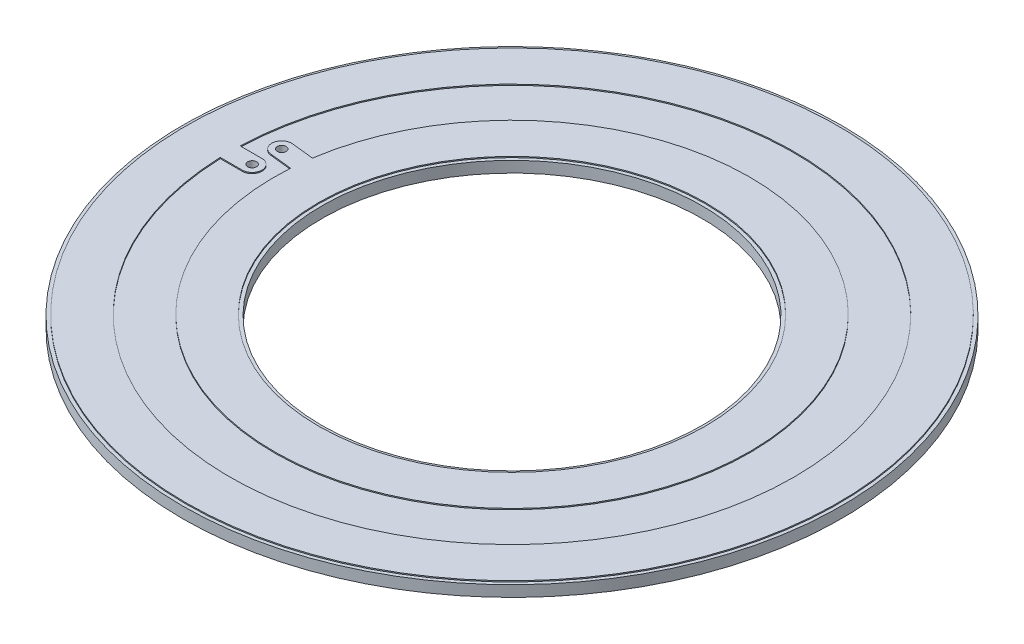
SolidWorks part; units mm, degrees
ref_plane "Спереди" through (0, 0, 0) normal (0, 0, 1) x (1, 0, 0)
ref_plane "Сверху" through (0, 0, 0) normal (0, 1, 0) x (1, 0, 0)
ref_plane "Справа" through (0, 0, 0) normal (1, 0, 0) x (0, 0, -1)
sketch "Эскиз1" plane through (0, 0, 0) normal (0, 1, 0) x (1, 0, 0)
  circle A0 centre (0, 0) radius 17.2
  circle A1 centre (0, 0) radius 29.8
  dimension "D1" = 34.4
  dimension "D2" = 59.6
extrude "Бобышка-Вытянуть1" add sketch "Эскиз1" along normal blind 1
sketch "Эскиз2" plane through (0, 1, 0) normal (0, 1, 0) x (1, 0, 0)
  circle A0 centre (0, 0) radius 29.5
  circle A1 centre (0, 0) radius 25.5
  circle A2 centre (0, 0) radius 21.5
  circle A3 centre (0, 0) radius 17.5
  circle A5 centre (0, 0) radius 17.2 construction
  dimension "D1" = 4
  dimension "D2" = 4
  dimension "D3" = 4
  dimension "D4" = 0.3
extrude "Бобышка-Вытянуть2" add sketch "Эскиз2" along normal blind 0.1 contours A2 A3 | A0 A1 region at (-28.6656, 1, 0) region at (-20.8919, 1, 0)
sketch "Эскиз4" plane through (0, 1, 0) normal (0, 1, 0) x (1, 0, 0)
  line L0 (0, 0) -> (-33.7363, 0) construction
  circle A0 centre (-23.5, 0) radius 0.4
  circle A1 centre (-23.3623, 2.54) radius 0.4
  circle A3 centre (0, 0) radius 23.5 construction
  circle A4 centre (0, 0) radius 21.5 construction
  dimension "D1" = 2
  dimension "D2" = 0.8
  dimension "D3" = 0.8
  dimension "D5" = 47
  dimension "D4" = 2.54
extrude "Вырез-Вытянуть1" cut sketch "Эскиз4" against normal through all
sketch "Эскиз5" plane through (0, 1, 0) normal (0, 1, 0) x (1, 0, 0)
  circle A0 centre (-23.3623, 2.54) radius 0.9
  circle A1 centre (-23.5, 0) radius 0.4 construction
  circle A3 centre (-23.5, 0) radius 0.9
  circle A4 centre (-23.5, 0) radius 0.4
  circle A5 centre (-23.3623, 2.54) radius 0.4 construction
  circle A6 centre (-23.3623, 2.54) radius 0.4
  dimension "D2" = 1.8
  dimension "D1" = 1.8
extrude "Бобышка-Вытянуть3" add sketch "Эскиз5" along normal blind 0.1
ref_axis "Ось1" through (0, 1, 0) along (0, -1, 0)
sketch "Эскиз6" plane through (0, 1, 0) normal (0, 1, 0) x (1, 0, 0)
  line L2 (-23.3623, 2.54) -> (0, 0) construction
  line L5 (-23.5, -0.9) -> (-27.4565, -0.9)
  line L6 (-23.5, 0.9) -> (-27.4565, 0.9)
  line L7 (-27.4565, 0.9) -> (-27.4565, -0.9)
  line L8 (-23.5, -0.9) -> (-24.1108, 0)
  line L9 (-24.1108, 0) -> (-23.5, 0.9)
  line L10 (-23.3623, 1.64) -> (-20.0181, 1.2764)
  line L11 (-20.0181, 1.2764) -> (-19.8247, 3.0554)
  line L12 (-23.1689, 3.419) -> (-19.8247, 3.0554)
  line L13 (-23.3623, 1.64) -> (-22.768, 2.4754)
  line L14 (-22.768, 2.4754) -> (-23.1689, 3.419)
  circle A0 centre (-23.3623, 2.54) radius 0.9 construction
  circle A19 centre (-23.5, 0) radius 0.9 construction
  circle A20 centre (-23.5, 0) radius 0.9 construction
  point P16 (-19.9214, 2.1659)
extrude "Бобышка-Вытянуть4" add sketch "Эскиз6" along normal blind 0.1
